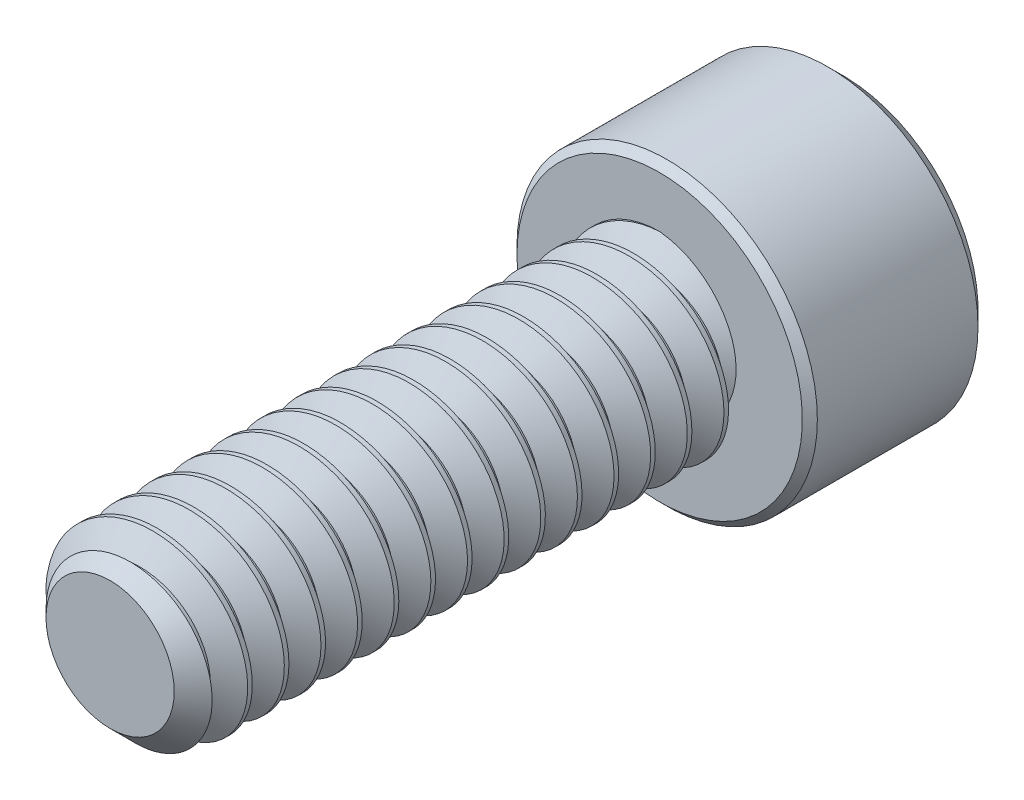
SolidWorks part; units mm, degrees
ref_plane "Front Plane" through (0, 0, 0) normal (0, 0, 1) x (1, 0, 0)
ref_plane "Top Plane" through (0, 0, 0) normal (0, 1, 0) x (1, 0, 0)
ref_plane "Right Plane" through (0, 0, 0) normal (1, 0, 0) x (0, 0, -1)
sketch "Sketch0" plane through (0, 0, 0) normal (1, 0, 0) x (0, 0, -1)
  line L0 (0, 0) -> (9.525, 0) construction
  point P2 (12.7, 0)
  point P4 (0, 0)
  dimension "D1" = 9.525
  dimension "D2" = 3.175
  dimension "Min Thread" = 0
sketch "Sketch1" plane through (0, 0, 0) normal (0, 0, 1) x (1, 0, 0)
  circle A0 centre (0, 0) radius 1.5875
  dimension "OD" = 3.175
extrude "Extrude1" add sketch "Sketch1" against normal blind 9.525
sketch "Sketch2" plane through (0, 0, 0) normal (0, 0, 1) x (1, 0, 0)
  circle A0 centre (0, 0) radius 1.5875 construction
  circle A1 centre (0, 0) radius 1.5875
curve "Helix/Spiral1" pitch 0.635 height 10.16 radius 1.5875 centre (0, 0, 0) axis (0, 0, -1) start towards (0, 1, 0) parameters "pitch"=0.635
chamfer "Chamfer3" distance 0.4763 angle 45 1 edges at (1.5875, 0, 0)
sketch "Sketch3" plane through (0, 0, 0) normal (1, 0, 0) x (0, 0, -1)
  line L0 (-0.5556, 1.5875) -> (-0.3175, 1.1751)
  line L1 (-0.3175, 1.1751) -> (-0.2381, 1.1751)
  line L2 (-0.2381, 1.1751) -> (0, 1.5875)
  line L3 (-0.5556, 1.5875) -> (0, 1.5875)
  line L4 (-0.2778, 1.5875) -> (-0.2778, 1.1751) construction
  line L5 (-0.4366, 1.3813) -> (-0.1191, 1.3813) construction
  line L6 (0, 1.5875) -> (0, -1.5875) construction
  dimension "D1" = 0.0794
  dimension "D2" = 0.3175
  dimension "D3" = 60
sweep "Cut-Sweep1" cut profiles "Sketch3" path "Helix/Spiral1" align with end faces yes
sketch "Sketch5" plane through (0, 0, 0) normal (1, 0, 0) x (0, 0, -1)
  line L0 (9.525, -1.1864) -> (9.525, 1.1327) construction
  line L1 (9.525, 1.5875) -> (0, 1.5875)
  line L2 (9.525, 1.5875) -> (9.525, 0)
  line L3 (9.525, 0) -> (-0.5778, 0)
  line L4 (0, 0) -> (9.525, 0) construction
  line L5 (0, 1.5875) -> (-0.5778, 0)
  line L6 (0, 0) -> (12.065, 0) construction
  dimension "D1" = 70
  dimension "D3" = 2.54
revolve "partially thread" [suppressed] add sketch "Sketch5" angle 360 about L6
sketch "Sketch6" plane through (0, 0, -9.525) normal (0, 0, -1) x (-1, 0, 0)
  circle A0 centre (0, 0) radius 2.6035
  dimension "head dia" = 5.207
extrude "Extrude2" add sketch "Sketch6" along normal blind 3.175
sketch "Sketch7" plane through (0, 0, -12.7) normal (0, 0, -1) x (-1, 0, 0)
  line L1 (0, 1.3748) -> (-1.1906, 0.6874)
  line L2 (-1.1906, 0.6874) -> (-1.1906, -0.6874)
  line L3 (-1.1906, -0.6874) -> (0, -1.3748)
  line L4 (0, -1.3748) -> (1.1906, -0.6874)
  line L5 (1.1906, -0.6874) -> (1.1906, 0.6874)
  line L6 (1.1906, 0.6874) -> (0, 1.3748)
  circle A0 centre (0, 0) radius 1.1906 construction
  dimension "hex dia" = 2.3813
extrude "Cut-Extrude1" cut sketch "Sketch7" against normal blind 1.7859
sketch "Sketch8" plane through (0, 0, -12.7) normal (0, 0, -1) x (-1, 0, 0)
  circle A0 centre (0, 0) radius 1.3748
extrude "Cut-Extrude2" cut sketch "Sketch8" against normal through all draft 45
chamfer "Chamfer1" distance 0.2604 angle 45 1 edges at (-2.6035, 0, -12.7)
chamfer "Chamfer2" distance 0.1302 angle 45 1 edges at (-2.6035, 0, -9.525)
sketch "Sketch9" plane through (0, 0, 0) normal (1, 0, 0) x (0, 0, -1)
  line L0 (0, 1.5875) -> (0, -1.5875) construction
  line L1 (1.5875, 1.5875) -> (1.5875, -1.5875) construction
  line L2 (12.7, 2.6035) -> (12.7, -2.6035) construction
  line L3 (9.525, 2.6035) -> (9.525, -2.6035) construction
  line L4 (9.525, 2.4733) -> (9.525, -2.4733) construction
  line L5 (12.7, -2.3431) -> (12.7, 2.3431) construction
  line L6 (9.525, -2.6035) -> (9.525, 2.6035) construction
  line L7 (0, 1.1113) -> (0, -1.1113) construction
  line L8 (-0.5556, 1.5875) -> (0, 1.5875) construction
  line L9 (1.5875, 0) -> (0, 0) construction
  dimension "D1" = 1.5875
equation "\"D3@Helix/Spiral1\" = \"screw length@Extrude1\"+\"pitch@Helix/Spiral1\""
equation "\"D1@Sketch3\" = \"pitch@Helix/Spiral1\"*.125"
equation "\"D2@Sketch3\" = \"pitch@Helix/Spiral1\"*.5"
equation "\"D1@Cut-Extrude1\" = \"hex dia@Sketch7\"*.75"
equation "\"D1@Chamfer1\" = \"head dia@Sketch6\"*.05"
equation "\"D1@Sketch9\" = \"pitch@Helix/Spiral1\"*2.50"
equation "\"D1@Chamfer2\" = \"D1@Chamfer1\"/2"
equation "\"D1@Chamfer3\" = \"pitch@Helix/Spiral1\"*.750"
equation "\"D1@Sketch0\" = \"screw length@Extrude1\""
equation "\"D2@Sketch0\" = \"head depth@Extrude2\""
